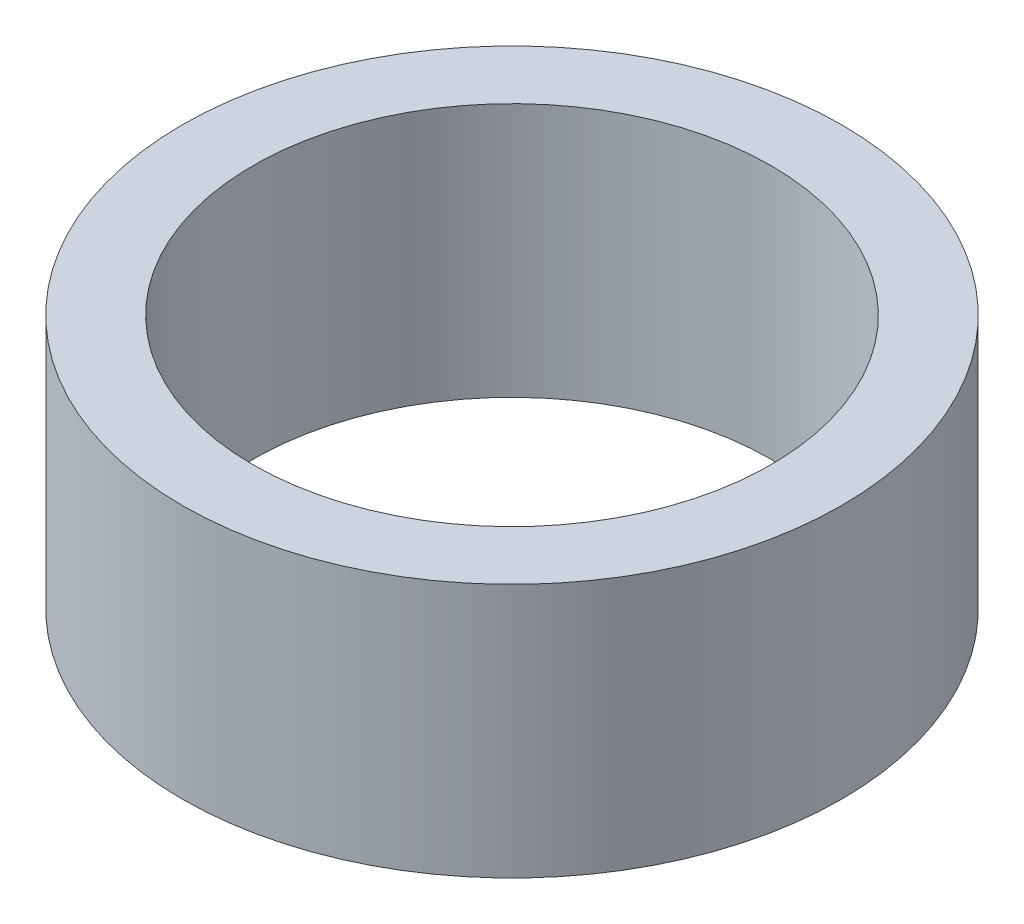
SolidWorks part; units mm, degrees
ref_plane "Front Plane" through (0, 0, 0) normal (0, 0, 1) x (1, 0, 0)
ref_plane "Top Plane" through (0, 0, 0) normal (0, 1, 0) x (1, 0, 0)
ref_plane "Right Plane" through (0, 0, 0) normal (1, 0, 0) x (0, 0, -1)
sketch "Sketch1" plane through (0, 0, 0) normal (0, 1, 0) x (1, 0, 0)
  circle A0 centre (0, 0) radius 35
  dimension "FLANGE_OD" = 70
extrude "Boss-Extrude1" add sketch "Sketch1" along normal blind 27
sketch "Sketch2" plane through (0, 0, 0) normal (0, 1, 0) x (1, 0, 0)
  circle A0 centre (0, 0) radius 27.5
  dimension "BORE_D" = 55
extrude "Cut-Extrude1" cut sketch "Sketch2" along normal through all
sketch "Sketch3" plane through (0, 27, 0) normal (0, 1, 0) x (1, 0, 0)
  circle A0 centre (0, 0) radius 15.6216 construction
  circle A1 centre (-15.6216, 0) radius 1.5
  dimension "BOLT_D" = 3
  dimension "BOLT_PCD" = 31.2433
extrude "Cut-Extrude2" cut sketch "Sketch3" against normal blind 25.904 rebuild error yes
pattern_circular "CirPattern1" count 6 over 360 rebuild error yes
